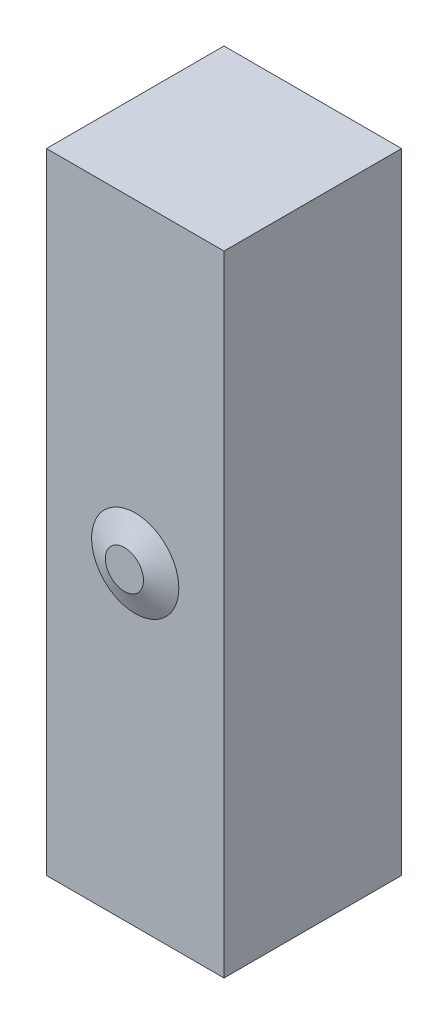
SolidWorks part; units mm, degrees
ref_plane "Front Plane" through (0, 0, 0) normal (0, 0, 1) x (1, 0, 0)
ref_plane "Top Plane" through (0, 0, 0) normal (0, 1, 0) x (1, 0, 0)
ref_plane "Right Plane" through (0, 0, 0) normal (1, 0, 0) x (0, 0, -1)
sketch "Sketch1" plane through (0, 0, 0) normal (0, 0, 1) x (1, 0, 0)
  line L1 (-8.25, -29.25) -> (8.25, -29.25)
  line L2 (-8.25, -29.25) -> (-8.25, 29.25)
  line L3 (-8.25, 29.25) -> (8.25, 29.25)
  line L4 (8.25, -29.25) -> (8.25, 29.25)
  line L5 (-8.25, -29.25) -> (8.25, 29.25) construction
  line L6 (-8.25, 29.25) -> (8.25, -29.25) construction
  point P0 (0, 0)
extrude "Boss-Extrude1" add sketch "Sketch1" along normal blind 16.5
sketch "Sketch4" plane through (0, 0, 16.5) normal (0, 0, 1) x (1, 0, 0)
  circle A0 centre (0, 0) radius 4.05
  circle A1 centre (0, 0) radius 1.77
extrude "Boss-Extrude6" add sketch "Sketch4" along normal blind 1 contours A1
loft "Loft3" add section "Sketch4<16>" section edge at (1.77, 0, 17.5)
sketch "Sketch4<16>" plane through (0, 0, 16.5) normal (0, 0, 1) x (1, 0, 0) same geometry as "Sketch4"
